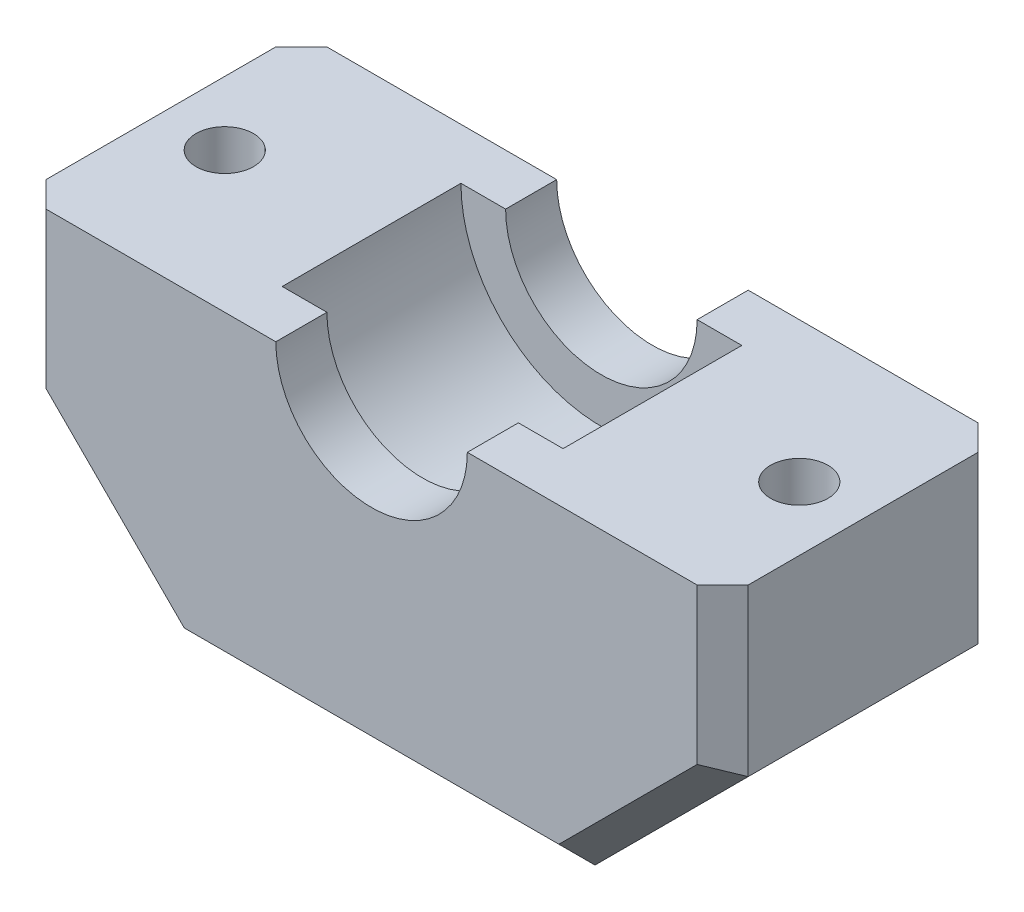
SolidWorks part; units mm, degrees
other "Markup1"
sketch "Sketch6" plane through (-48.9855, -22.9711, -22) normal (-0.4915, -0.8705, -0.0256) x (-0.8683, 0.4921, -0.0625)
ref_plane "Front Plane" through (0, 0, 0) normal (0, 0, 1) x (1, 0, 0)
ref_plane "Top Plane" through (0, 0, 0) normal (0, 1, 0) x (1, 0, 0)
ref_plane "Right Plane" through (0, 0, 0) normal (1, 0, 0) x (0, 0, -1)
sketch "Sketch1" plane through (0, 0, 0) normal (0, 0, -1) x (1, 0, 0)
  line L0 (-38.9855, -2.0289) -> (-48.9855, -2.0289)
  line L1 (-48.9855, -2.0289) -> (-48.9855, 22.9711)
  line L2 (-48.9855, 22.9711) -> (6.0145, 22.9711)
  line L3 (6.0145, 22.9711) -> (6.0145, -2.0289)
  line L4 (6.0145, -2.0289) -> (-3.9855, -2.0289)
  arc A0 (-38.9855, -2.0289) -> (-3.9855, -2.0289) centre (-21.4855, -2.0289) cw
  dimension "D1" = 17.5
  dimension "D2" = 10
  dimension "D3" = 25
extrude "Boss-Extrude1" add sketch "Sketch1" along normal blind 22
chamfer "Chamfer1" distance 12 distance2 12 2 edges at (6.0145, -22.9711, -11) (-48.9855, -22.9711, -11)
sketch "Sketch2" plane through (0, -22.9711, 0) normal (0, -1, 0) x (-1, 0, 0)
  line L0 (48.9855, 22) -> (48.9855, 0) construction
  line L1 (-6.0145, 22) -> (-6.0145, 0) construction
  line L2 (5.9855, 0) -> (36.9855, 0) construction
  circle A0 centre (-1.0145, 11) radius 2.25
  circle A1 centre (43.9855, 11) radius 2.25
  circle A2 centre (43.9855, 11) radius 4.5
  circle A3 centre (-1.0145, 11) radius 4.5
  point P8 (-6.0145, 11)
  dimension "D4" = 4.5
  dimension "D5" = 9
  dimension "D1" = 5
  dimension "D2" = 5
  dimension "D3" = 11
extrude "Cut-Extrude1" cut sketch "Sketch2" against normal up to surface (25 mm away) contours A1 | A0 region at (1.0145, -22.9711, -11) region at (-43.9855, -22.9711, -11) up to face at (-43.9855, 2.0289, -11)
extrude "Cut-Extrude2" cut sketch "Sketch2<4>" against normal offset from surface (21 mm away) 4 up to face at (-41.7355, 2.0289, -11)
sketch "Sketch2<4>" plane through (0, -22.9711, 0) normal (0, -1, 0) x (-1, 0, 0) same geometry as "Sketch2"
chamfer "Chamfer2" distance 2 angle 45 10 edges at (-48.9855, -4.4711, 0) (-42.9855, -16.9711, 0) (6.0145, -4.4711, 0) (-21.4855, -22.9711, 0) (0.0145, -16.9711, 0) (6.0145, -4.4711, -22) (-48.9855, -4.4711, -22) (-42.9855, -16.9711, -22) (-21.4855, -22.9711, -22) (0.0145, -16.9711, -22)
sketch "Sketch3" plane through (0, 0, -22) normal (0, 0, -1) x (-1, 0, 0)
  line L1 (3.9855, 2.0289) -> (10.4855, 2.0289)
  line L2 (32.4855, 2.0289) -> (38.9855, 2.0289)
  arc A0 (3.9855, 2.0289) -> (38.9855, 2.0289) centre (21.4855, 2.0289) ccw
  arc A1 (10.4855, 2.0289) -> (32.4855, 2.0289) centre (21.4855, 2.0289) ccw
  dimension "D1" = 35
  dimension "D2" = 22
extrude "Boss-Extrude2" add sketch "Sketch3" against normal up to surface (22 mm away) up to face at (-21.4855, -8.9515, 0)
sketch "Sketch4" plane through (0, 0, 0) normal (0, 0, 1) x (1, 0, 0)
  line L0 (-32.4855, 2.0289) -> (-28.9855, 2.0289)
  line L1 (-10.4855, 2.0289) -> (-13.9855, 2.0289)
  arc A0 (-32.4855, 2.0289) -> (-10.4855, 2.0289) centre (-21.4855, 2.0289) ccw
  arc A1 (-28.9855, 2.0289) -> (-13.9855, 2.0289) centre (-21.4855, 2.0289) ccw
  dimension "D2" = 15
extrude "Boss-Extrude3" add sketch "Sketch4" against normal blind 4
sketch "Sketch5" plane through (0, 0, -22) normal (0, 0, -1) x (-1, 0, 0)
  line L0 (10.4855, 2.0289) -> (13.9855, 2.0289)
  line L1 (32.4855, 2.0289) -> (28.9855, 2.0289)
  arc A0 (10.4855, 2.0289) -> (32.4855, 2.0289) centre (21.4855, 2.0289) ccw
  arc A1 (13.9855, 2.0289) -> (28.9855, 2.0289) centre (21.4855, 2.0289) ccw
extrude "Boss-Extrude4" add sketch "Sketch5" against normal blind 4
